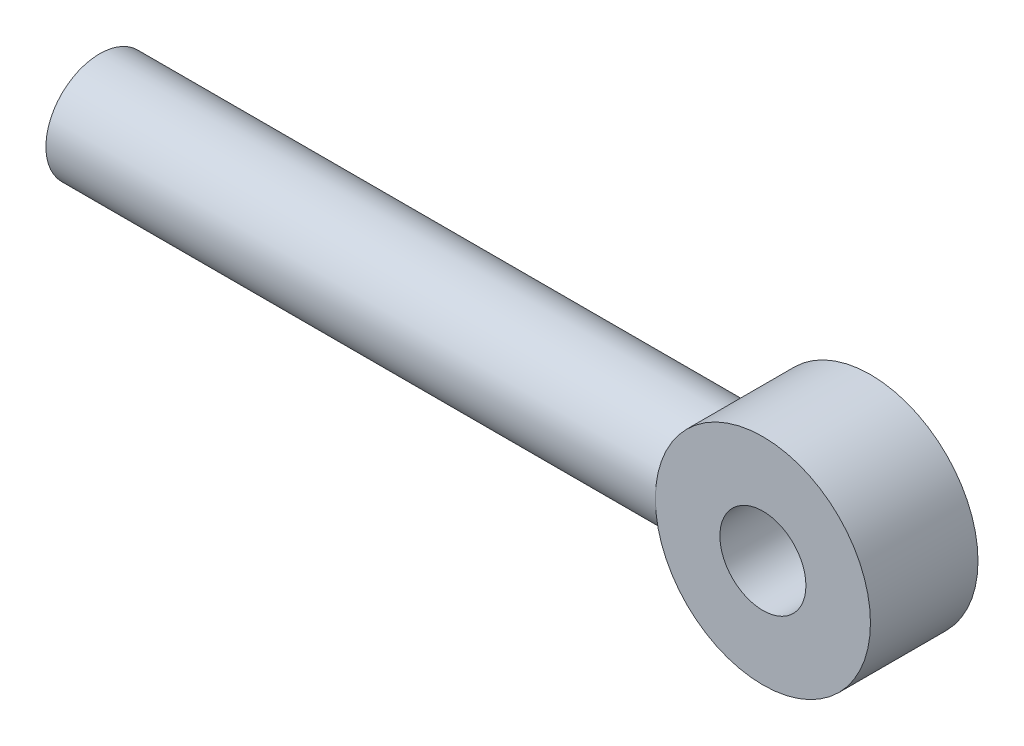
SolidWorks part; units mm, degrees
ref_plane "Front Plane" through (0, 0, 0) normal (0, 0, 1) x (1, 0, 0)
ref_plane "Top Plane" through (0, 0, 0) normal (0, 1, 0) x (1, 0, 0)
ref_plane "Right Plane" through (0, 0, 0) normal (1, 0, 0) x (0, 0, -1)
sketch "Sketch1" plane through (0, 0, 0) normal (1, 0, 0) x (0, 0, -1)
  circle A0 centre (0, 0) radius 0.75
  dimension "D1" = 1.5
extrude "Boss-Extrude1" add sketch "Sketch1" along normal blind 10
sketch "Sketch2" plane through (0, 0, 0) normal (0, 0, 1) x (1, 0, 0)
  line L0 (10, -0.75) -> (10, 0.75) construction
  circle A0 centre (10, 0) radius 1.5
  dimension "D1" = 3
extrude "Boss-Extrude2" add sketch "Sketch2" along normal blind 0.75 and the other way blind 0.75
sketch "Sketch3" plane through (0, 0, 0.75) normal (0, 0, 1) x (1, 0, 0)
  circle A0 centre (10, 0) radius 0.6
  circle A1 centre (10, 0) radius 1.5 construction
  dimension "D2" = 1.2
  dimension "D1" = 0
extrude "Cut-Extrude1" cut sketch "Sketch3" against normal blind 1.5
